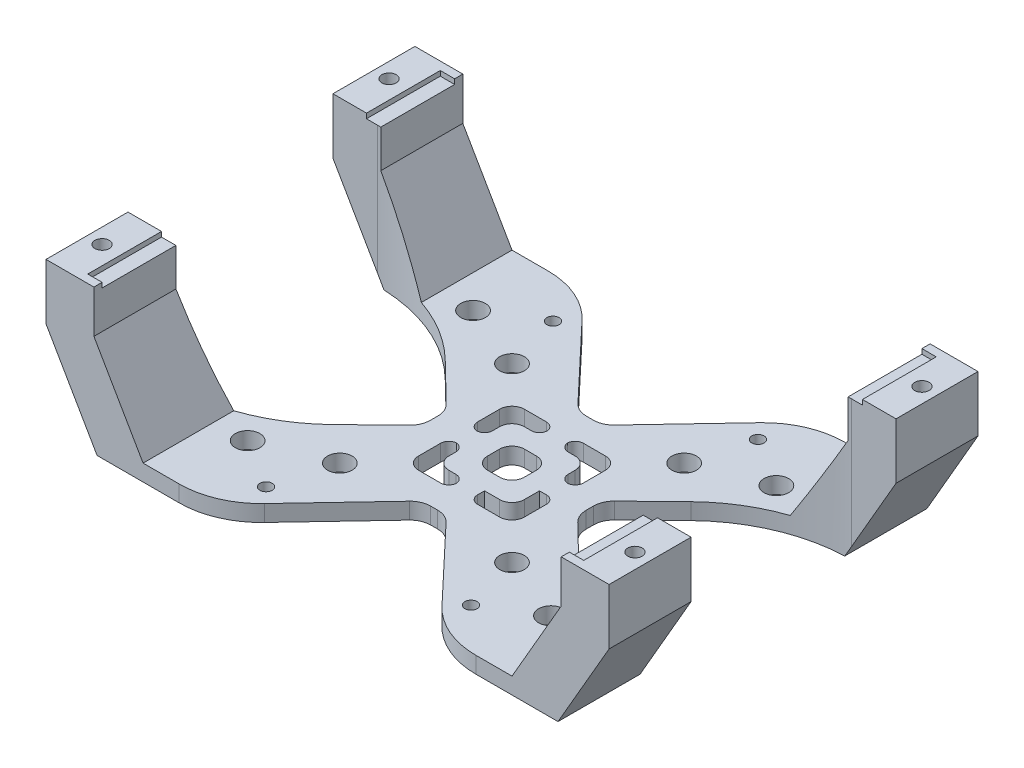
SolidWorks part; units mm, degrees
ref_plane "Спереди" through (0, 0, 0) normal (0, 0, 1) x (1, 0, 0)
ref_plane "Сверху" through (0, 0, 0) normal (0, 1, 0) x (1, 0, 0)
ref_plane "Справа" through (0, 0, 0) normal (1, 0, 0) x (0, 0, -1)
other "Configuration Table"
sketch "Эскиз1" plane through (0, 0, 0) normal (0, 1, 0) x (1, 0, 0)
  line L0 (-1000, 0) -> (49000, 0) construction
  line L1 (0, -1000) -> (0, 49000) construction
  line L2 (19, -0.8894) -> (19, 0.8894)
  line L7 (0, 19) -> (0.8457, 19)
  line L9 (20.5123, 4.4722) -> (40.4877, 23.9172)
  line L10 (4.4797, 20.5658) -> (21.366, 38.4342)
  line L11 (27.65, 39.24) -> (39.65, 31.74)
  line L12 (27.65, -39.24) -> (39.65, -31.74)
  line L13 (4.4797, -20.5658) -> (21.366, -38.4342)
  line L14 (20.5123, -4.4722) -> (40.4877, -23.9172)
  line L15 (0, -19) -> (0.8457, -19)
  line L16 (-20.5123, -4.4722) -> (-40.4877, -23.9172)
  line L17 (-4.4797, -20.5658) -> (-21.366, -38.4342)
  line L18 (-27.65, -39.24) -> (-39.65, -31.74)
  line L19 (-27.65, 39.24) -> (-39.65, 31.74)
  line L20 (-4.4797, 20.5658) -> (-21.366, 38.4342)
  line L21 (-20.5123, 4.4722) -> (-40.4877, 23.9172)
  line L22 (-19, -0.8894) -> (-19, 0.8894)
  line L23 (-0.8457, -19) -> (0, -19)
  line L24 (-0.8457, 19) -> (0, 19)
  line L25 (-21, 21) -> (21, -21) construction
  line L26 (-21, -21) -> (21, 21) construction
  line L27 (-2.5, 9.2035) -> (-2.5, 12.906)
  line L28 (-12.906, -12.906) -> (12.906, -12.906)
  line L29 (-12.906, -12.906) -> (-12.906, 12.906)
  line L30 (-12.906, 12.906) -> (12.906, 12.906)
  line L31 (12.906, -12.906) -> (12.906, 12.906)
  line L32 (-12.906, -12.906) -> (12.906, 12.906) construction
  line L33 (-12.906, 12.906) -> (12.906, -12.906) construction
  line L34 (-9.2035, -9.2035) -> (9.2035, -9.2035)
  line L35 (-9.2035, -9.2035) -> (-9.2035, 9.2035)
  line L36 (-9.2035, 9.2035) -> (9.2035, 9.2035)
  line L37 (9.2035, -9.2035) -> (9.2035, 9.2035)
  line L38 (-9.2035, -9.2035) -> (9.2035, 9.2035) construction
  line L39 (-9.2035, 9.2035) -> (9.2035, -9.2035) construction
  line L40 (-4.4797, -4.4797) -> (4.4797, -4.4797)
  line L41 (-4.4797, -4.4797) -> (-4.4797, 4.4797)
  line L42 (-4.4797, 4.4797) -> (4.4797, 4.4797)
  line L43 (4.4797, -4.4797) -> (4.4797, 4.4797)
  line L44 (-4.4797, -4.4797) -> (4.4797, 4.4797) construction
  line L45 (-4.4797, 4.4797) -> (4.4797, -4.4797) construction
  line L46 (2.5, 9.2035) -> (2.5, 12.906)
  line L47 (2.5, -9.2035) -> (2.5, -12.906)
  line L48 (-2.5, -9.2035) -> (-2.5, -12.906)
  line L49 (-9.2035, -2.5) -> (-12.906, -2.5)
  line L50 (-9.2035, 2.5) -> (-12.906, 2.5)
  line L51 (9.2035, 2.5) -> (12.906, 2.5)
  line L52 (9.2035, -2.5) -> (12.906, -2.5)
  circle A12 centre (25, 35) radius 1.5
  circle A13 centre (21, 21) radius 3
  circle A14 centre (37, 27.5) radius 3
  circle A15 centre (37, 27.5) radius 5
  circle A16 centre (21, 21) radius 5
  circle A17 centre (25, 35) radius 5
  circle A18 centre (25, -35) radius 5
  circle A19 centre (21, -21) radius 5
  circle A20 centre (37, -27.5) radius 5
  circle A21 centre (37, -27.5) radius 3
  circle A22 centre (21, -21) radius 3
  circle A23 centre (25, -35) radius 1.5
  circle A24 centre (-25, -35) radius 1.5
  circle A25 centre (-21, -21) radius 3
  circle A26 centre (-37, -27.5) radius 3
  circle A27 centre (-37, -27.5) radius 5
  circle A28 centre (-21, -21) radius 5
  circle A29 centre (-25, -35) radius 5
  circle A30 centre (-25, 35) radius 5
  circle A31 centre (-21, 21) radius 5
  circle A32 centre (-37, 27.5) radius 5
  circle A33 centre (-37, 27.5) radius 3
  circle A34 centre (-21, 21) radius 3
  circle A35 centre (-25, 35) radius 1.5
  arc A36 (19, 0.8894) -> (20.5123, 4.4722) centre (24, 0.8894) cw
  arc A37 (20.5123, -4.4722) -> (19, -0.8894) centre (24, -0.8894) cw
  arc A38 (4.4797, -20.5658) -> (0.8457, -19) centre (0.8457, -24) ccw
  arc A39 (-4.4797, -20.5658) -> (-0.8457, -19) centre (-0.8457, -24) cw
  arc A40 (-20.5123, -4.4722) -> (-19, -0.8894) centre (-24, -0.8894) ccw
  arc A41 (-20.5123, 4.4722) -> (-19, 0.8894) centre (-24, 0.8894) cw
  arc A42 (0.8457, 19) -> (4.4797, 20.5658) centre (0.8457, 24) ccw
  arc A43 (-4.4797, 20.5658) -> (-0.8457, 19) centre (-0.8457, 24) ccw
  point P41 (19, 0)
  point P71 (-19, 0)
  point P74 (19, 3)
  point P77 (19, -3)
  point P80 (3, -19)
  point P83 (-3, -19)
  point P86 (-19, -3)
  point P89 (-19, 3)
  point P92 (3, 19)
  point P95 (-3, 19)
  point P96 (0, 0)
  point P101 (0, 0)
  point P106 (0, 0)
  dimension "D3" = 6
  dimension "D8" = 37
  dimension "D19" = 5
  dimension "D1" = 3
  dimension "D2" = 6
  dimension "D14" = 10
  dimension "D15" = 10
  dimension "D16" = 10
  dimension "D17" = 5
  dimension "D4" = 35
  dimension "D5" = 25
  dimension "D6" = 21
  dimension "D7" = 21
  dimension "D9" = 27.5
  dimension "D10" = 19
  dimension "D11" = 19
  dimension "D12" = 3
  dimension "D13" = 3
  dimension "D18" = 5
extrude "Бобышка-Вытянуть1" add sketch "Эскиз1" along normal blind 4 contours L19 A32 L21 L22 L16 A27 L18 A29 L17 L23 L15 L13 A18 L12 A20 L14 L2 L9 A15 L11 A17 L10 L7 L24 L20 A30 A31 A28 A16 A19 | A18 A23 | A19 A22 | A20 A21 | A29 A24 | A27 A26 | A28 A25 | A16 A13 | A17 A12 | A15 A14 | A31 A34 | A30 A35 | A32 A33 | L40 L43 L42 L41 | L34 L48 L28 L47 | L35 L50 L29 L49 | L37 L52 L31 L51 | L36 L46 L30 L27 | L35 L34 L37 L36 region at (18.3547, 0, 3.2724) region at (41.4761, 0, 25.6106) region at (32.169, 0, -26.9827) region at (24.3821, 0, 39.8191) region at (29.2495, 0, -37.3553) region at (-24.3821, 0, 39.8191) region at (-20.4854, 0, -36.7957) region at (-41.831, 0, 28.0173) region at (-34.6447, 0, -31.7495) region at (0, 0, -11.0548) region at (-11.0548, 0, 0) region at (11.0548, 0, 0) region at (0, 0, 11.0548) region at (0, 0, 0) region at (16.1414, 0, -21) region at (16.1414, 0, 21) region at (-25.8586, 0, 21) region at (-25.8586, 0, -21)
fillet "Скругление6" radius 3 4 edges at (-4.4797, 2, 4.4797) (4.4797, 2, 4.4797) (4.4797, 2, -4.4797) (-4.4797, 2, -4.4797)
fillet "Скругление7" radius 3 8 edges at (-12.906, 2, 12.906) (12.906, 2, 12.906) (12.906, 2, -12.906) (-12.906, 2, -12.906) (9.2035, 2, 9.2035) (-9.2035, 2, 9.2035) (-9.2035, 2, -9.2035) (9.2035, 2, -9.2035)
fillet "Скругление8" radius 2 14 edges at (-2.5, 2, 12.906) (-2.5, 2, 9.2035) (12.906, 2, 2.5) (12.906, 2, -2.5) (2.5, 2, 12.906) (9.2035, 2, -2.5) (2.5, 2, -9.2035) (2.5, 2, -12.906) (-2.5, 2, -12.906) (-2.5, 2, -9.2035) (-9.2035, 2, -2.5) (-12.906, 2, -2.5) (-9.2035, 2, 2.5) (-12.906, 2, 2.5)
sketch "Эскиз5" plane through (0, 4, 0) normal (0, 1, 0) x (1, 0, 0)
  line L0 (-1000, 0) -> (49000, 0) construction
  line L1 (0, -1000) -> (0, 49000) construction
  line L2 (57.8542, 25) -> (60, 25)
  line L7 (-60, -45) -> (60, -45) construction
  line L8 (-60, -45) -> (-60, 45) construction
  line L9 (-60, 45) -> (60, 45) construction
  line L10 (60, -45) -> (60, 45) construction
  line L11 (-60, -45) -> (60, 45) construction
  line L12 (-60, 45) -> (60, -45) construction
  line L13 (60, 45) -> (65, 45)
  line L14 (60, 45) -> (60, 25)
  line L15 (60, 25) -> (65, 25)
  line L16 (65, 45) -> (65, 25)
  line L17 (20.5123, 4.4722) -> (40.4877, 23.9172) construction
  line L18 (15.9182, 0) -> (29.9529, 13.6622)
  line L19 (0, 15.8255) -> (21.6521, 38.737)
  line L22 (4.4797, 20.5658) -> (21.366, 38.4342) construction
  line L23 (36.1881, 45) -> (65, 45)
  line L24 (36.1881, -45) -> (65, -45)
  line L25 (0, -15.8255) -> (21.6521, -38.737)
  line L26 (15.9182, 0) -> (29.9529, -13.6622)
  line L27 (65, -45) -> (65, -25)
  line L28 (60, -25) -> (65, -25)
  line L29 (60, -45) -> (60, -25)
  line L30 (60, -45) -> (65, -45)
  line L31 (57.8542, -25) -> (60, -25)
  line L32 (60, 45) -> (-60, -45) construction
  line L33 (60, -45) -> (-60, 45) construction
  line L34 (-60, -45) -> (-60, 45) construction
  line L35 (-57.8542, -25) -> (-60, -25)
  line L36 (-60, -45) -> (-65, -45)
  line L37 (-60, -45) -> (-60, -25)
  line L38 (-60, -25) -> (-65, -25)
  line L39 (-65, -45) -> (-65, -25)
  line L40 (-15.9182, 0) -> (-29.9529, -13.6622)
  line L41 (0, -15.8255) -> (-21.6521, -38.737)
  line L42 (-36.1881, -45) -> (-65, -45)
  line L43 (-36.1881, 45) -> (-65, 45)
  line L44 (0, 15.8255) -> (-21.6521, 38.737)
  line L45 (-15.9182, 0) -> (-29.9529, 13.6622)
  line L46 (-65, 45) -> (-65, 25)
  line L47 (-60, 25) -> (-65, 25)
  line L48 (-60, 45) -> (-60, 25)
  line L49 (-60, 45) -> (-65, 45)
  line L50 (-57.8542, 25) -> (-60, 25)
  line L67 (-4.4797, 20.5658) -> (-21.366, 38.4342)
  line L68 (-27.65, 39.24) -> (-39.65, 31.74)
  line L69 (-40.4877, 23.9172) -> (-20.5123, 4.4722)
  line L70 (-19, 0.8894) -> (-19, -0.8894)
  line L71 (-20.5123, -4.4722) -> (-40.4877, -23.9172)
  line L72 (-39.65, -31.74) -> (-27.65, -39.24)
  line L73 (-21.366, -38.4342) -> (-4.4797, -20.5658)
  line L74 (-0.8457, -19) -> (0.8457, -19)
  line L75 (4.4797, -20.5658) -> (21.366, -38.4342)
  line L76 (27.65, -39.24) -> (39.65, -31.74)
  line L77 (40.4877, -23.9172) -> (20.5123, -4.4722)
  line L78 (19, -0.8894) -> (19, 0.8894)
  line L79 (20.5123, 4.4722) -> (40.4877, 23.9172)
  line L80 (39.65, 31.74) -> (27.65, 39.24)
  line L81 (21.366, 38.4342) -> (4.4797, 20.5658)
  line L82 (0.8457, 19) -> (-0.8457, 19)
  line L83 (-4.4797, 20.5658) -> (-21.366, 38.4342)
  line L84 (-27.65, 39.24) -> (-39.65, 31.74)
  line L85 (-40.4877, 23.9172) -> (-20.5123, 4.4722)
  line L86 (-19, 0.8894) -> (-19, -0.8894)
  line L87 (-20.5123, -4.4722) -> (-40.4877, -23.9172)
  line L88 (-39.65, -31.74) -> (-27.65, -39.24)
  line L89 (-21.366, -38.4342) -> (-4.4797, -20.5658)
  line L90 (-0.8457, -19) -> (0.8457, -19)
  line L91 (4.4797, -20.5658) -> (21.366, -38.4342)
  line L92 (27.65, -39.24) -> (39.65, -31.74)
  line L93 (40.4877, -23.9172) -> (20.5123, -4.4722)
  line L94 (19, -0.8894) -> (19, 0.8894)
  line L95 (20.5123, 4.4722) -> (40.4877, 23.9172)
  line L96 (39.65, 31.74) -> (27.65, 39.24)
  line L97 (21.366, 38.4342) -> (4.4797, 20.5658)
  line L98 (0.8457, 19) -> (-0.8457, 19)
  arc A0 (57.8542, 25) -> (29.9529, 13.6622) centre (57.8542, -15) ccw
  arc A1 (36.1881, 45) -> (21.6521, 38.737) centre (36.1881, 25) ccw
  arc A2 (36.1881, -45) -> (21.6521, -38.737) centre (36.1881, -25) cw
  arc A3 (57.8542, -25) -> (29.9529, -13.6622) centre (57.8542, 15) cw
  arc A4 (-57.8542, -25) -> (-29.9529, -13.6622) centre (-57.8542, 15) ccw
  arc A5 (-36.1881, -45) -> (-21.6521, -38.737) centre (-36.1881, -25) ccw
  arc A6 (-36.1881, 45) -> (-21.6521, 38.737) centre (-36.1881, 25) cw
  arc A7 (-57.8542, 25) -> (-29.9529, 13.6622) centre (-57.8542, -15) cw
  circle A8 centre (-37, 27.5) radius 3 construction
  circle A9 centre (-25, 35) radius 1.5 construction
  circle A10 centre (-21, 21) radius 3 construction
  circle A11 centre (-37, 27.5) radius 3
  circle A12 centre (-25, 35) radius 1.5
  circle A13 centre (-21, 21) radius 3
  arc A24 (-4.4797, 20.5658) -> (-0.8457, 19) centre (-0.8457, 24) ccw
  arc A25 (-21.366, 38.4342) -> (-27.65, 39.24) centre (-25, 35) ccw
  arc A26 (-39.65, 31.74) -> (-40.4877, 23.9172) centre (-37, 27.5) ccw
  arc A27 (-19, 0.8894) -> (-20.5123, 4.4722) centre (-24, 0.8894) ccw
  arc A28 (-20.5123, -4.4722) -> (-19, -0.8894) centre (-24, -0.8894) ccw
  arc A29 (-40.4877, -23.9172) -> (-39.65, -31.74) centre (-37, -27.5) ccw
  arc A30 (-27.65, -39.24) -> (-21.366, -38.4342) centre (-25, -35) ccw
  arc A31 (-0.8457, -19) -> (-4.4797, -20.5658) centre (-0.8457, -24) ccw
  arc A32 (4.4797, -20.5658) -> (0.8457, -19) centre (0.8457, -24) ccw
  arc A33 (21.366, -38.4342) -> (27.65, -39.24) centre (25, -35) ccw
  arc A34 (39.65, -31.74) -> (40.4877, -23.9172) centre (37, -27.5) ccw
  arc A35 (19, -0.8894) -> (20.5123, -4.4722) centre (24, -0.8894) ccw
  arc A36 (20.5123, 4.4722) -> (19, 0.8894) centre (24, 0.8894) ccw
  arc A37 (40.4877, 23.9172) -> (39.65, 31.74) centre (37, 27.5) ccw
  arc A38 (27.65, 39.24) -> (21.366, 38.4342) centre (25, 35) ccw
  arc A39 (0.8457, 19) -> (4.4797, 20.5658) centre (0.8457, 24) ccw
  arc A40 (-4.4797, 20.5658) -> (-0.8457, 19) centre (-0.8457, 24) ccw
  arc A41 (-21.366, 38.4342) -> (-27.65, 39.24) centre (-25, 35) ccw
  arc A42 (-39.65, 31.74) -> (-40.4877, 23.9172) centre (-37, 27.5) ccw
  arc A43 (-19, 0.8894) -> (-20.5123, 4.4722) centre (-24, 0.8894) ccw
  arc A44 (-20.5123, -4.4722) -> (-19, -0.8894) centre (-24, -0.8894) ccw
  arc A45 (-40.4877, -23.9172) -> (-39.65, -31.74) centre (-37, -27.5) ccw
  arc A46 (-27.65, -39.24) -> (-21.366, -38.4342) centre (-25, -35) ccw
  arc A47 (-0.8457, -19) -> (-4.4797, -20.5658) centre (-0.8457, -24) ccw
  arc A48 (4.4797, -20.5658) -> (0.8457, -19) centre (0.8457, -24) ccw
  arc A49 (21.366, -38.4342) -> (27.65, -39.24) centre (25, -35) ccw
  arc A50 (39.65, -31.74) -> (40.4877, -23.9172) centre (37, -27.5) ccw
  arc A51 (19, -0.8894) -> (20.5123, -4.4722) centre (24, -0.8894) ccw
  arc A52 (20.5123, 4.4722) -> (19, 0.8894) centre (24, 0.8894) ccw
  arc A53 (40.4877, 23.9172) -> (39.65, 31.74) centre (37, 27.5) ccw
  arc A54 (27.65, 39.24) -> (21.366, 38.4342) centre (25, 35) ccw
  arc A55 (0.8457, 19) -> (4.4797, 20.5658) centre (0.8457, 24) ccw
  point P4 (0, 0)
  point P6 (0, 0)
  point P24 (41.6, 25)
  point P30 (13.3997, 30.0046)
  point P35 (27.5709, 45)
  point P46 (27.5709, -45)
  point P47 (13.3997, -30.0046)
  point P48 (41.6, -25)
  point P68 (-41.6, -25)
  point P69 (-13.3997, -30.0046)
  point P70 (-27.5709, -45)
  point P71 (-27.5709, 45)
  point P72 (-13.3997, 30.0046)
  point P73 (-41.6, 25)
  dimension "D3" = 40
  dimension "D4" = 20
  dimension "D1" = 120
  dimension "D2" = 90
  dimension "D5" = 5
  dimension "D6" = 20
  dimension "D7" = 0
extrude "Бобышка-Вытянуть3" add sketch "Эскиз5" against normal up to surface (4 mm away) contours A42 L84 A41 L44 A6 L43 L48 L50 A7 L85 | L48 L43 L46 L47 | A46 L88 A45 L87 A4 L35 L37 L42 A5 L41 | L39 L36 L37 L38 | A50 L92 A49 L25 A2 L24 L29 L31 A3 L93 | L29 L24 L27 L28 | A54 L96 A53 L95 A0 L2 L14 L23 A1 L19 | L16 L13 L14 L15 region at (46.1694, 4, -35.4744) region at (62.5, 4, -35) region at (46.1694, 4, 35.4744) region at (62.5, 4, 35) region at (-46.1694, 4, -35.4744) region at (-62.5, 4, -35) region at (-46.1694, 4, 35.4744) region at (-62.5, 4, 35) up to face at (8.1977, 0, 8.1977)
sketch "Эскиз6" plane through (0, 4, 0) normal (0, 1, 0) x (1, 0, 0)
  line L0 (-1000, 0) -> (49000, 0) construction
  line L1 (65, 45) -> (60, 45)
  line L2 (65, 45) -> (65, 25)
  line L3 (65, 25) -> (60, 25)
  line L4 (-9.2035, -6.2035) -> (-9.2035, -4.5)
  line L5 (-4.5, -9.2035) -> (-6.2035, -9.2035)
  line L6 (-9.906, -12.906) -> (-4.5, -12.906)
  line L7 (-12.906, -4.5) -> (-12.906, -9.906)
  line L8 (-9.2035, -6.2035) -> (-9.2035, -4.5)
  line L9 (-4.5, -9.2035) -> (-6.2035, -9.2035)
  line L10 (-9.906, -12.906) -> (-4.5, -12.906)
  line L11 (-12.906, -4.5) -> (-12.906, -9.906)
  line L12 (4.4797, -1.4797) -> (4.4797, 1.4797)
  line L13 (-1.4797, -4.4797) -> (1.4797, -4.4797)
  line L14 (-4.4797, 1.4797) -> (-4.4797, -1.4797)
  line L15 (1.4797, 4.4797) -> (-1.4797, 4.4797)
  line L16 (4.4797, -1.4797) -> (4.4797, 1.4797)
  line L17 (-1.4797, -4.4797) -> (1.4797, -4.4797)
  line L18 (-4.4797, 1.4797) -> (-4.4797, -1.4797)
  line L19 (1.4797, 4.4797) -> (-1.4797, 4.4797)
  line L20 (9.2035, 6.2035) -> (9.2035, 4.5)
  line L21 (4.5, 9.2035) -> (6.2035, 9.2035)
  line L22 (9.906, 12.906) -> (4.5, 12.906)
  line L23 (12.906, 4.5) -> (12.906, 9.906)
  line L24 (9.2035, 6.2035) -> (9.2035, 4.5)
  line L25 (4.5, 9.2035) -> (6.2035, 9.2035)
  line L26 (9.906, 12.906) -> (4.5, 12.906)
  line L27 (12.906, 4.5) -> (12.906, 9.906)
  line L28 (-6.2035, 9.2035) -> (-4.5, 9.2035)
  line L29 (-9.2035, 4.5) -> (-9.2035, 6.2035)
  line L30 (-12.906, 9.906) -> (-12.906, 4.5)
  line L31 (-4.5, 12.906) -> (-9.906, 12.906)
  line L32 (-6.2035, 9.2035) -> (-4.5, 9.2035)
  line L33 (-9.2035, 4.5) -> (-9.2035, 6.2035)
  line L34 (-12.906, 9.906) -> (-12.906, 4.5)
  line L35 (-4.5, 12.906) -> (-9.906, 12.906)
  line L36 (60, 45) -> (60, 25)
  line L37 (0, -1000) -> (0, 49000) construction
  line L38 (6.2035, -9.2035) -> (2.5, -9.2035)
  line L39 (9.2035, -2.5) -> (9.2035, -6.2035)
  line L40 (10.906, -2.5) -> (9.2035, -2.5)
  line L41 (12.906, -9.906) -> (12.906, -4.5)
  line L42 (4.5, -12.906) -> (9.906, -12.906)
  line L43 (2.5, -9.2035) -> (2.5, -10.906)
  line L44 (6.2035, -9.2035) -> (2.5, -9.2035)
  line L45 (9.2035, -2.5) -> (9.2035, -6.2035)
  line L46 (10.906, -2.5) -> (9.2035, -2.5)
  line L47 (12.906, -9.906) -> (12.906, -4.5)
  line L48 (4.5, -12.906) -> (9.906, -12.906)
  line L49 (2.5, -9.2035) -> (2.5, -10.906)
  line L50 (57, 45) -> (57, 24.9909)
  line L51 (57, -45) -> (57, -24.9909)
  line L52 (-57, -45) -> (-57, -24.9909)
  line L53 (-57, 45) -> (-57, 24.9909)
  line L68 (4.4797, -20.5658) -> (21.6521, -38.737)
  line L69 (36.1881, -45) -> (65, -45)
  line L70 (65, -45) -> (65, -25)
  line L71 (65, -25) -> (57.8542, -25)
  line L72 (29.9529, -13.6622) -> (20.5123, -4.4722)
  line L73 (19, -0.8894) -> (19, 0.8894)
  line L74 (20.5123, 4.4722) -> (29.9529, 13.6622)
  line L75 (57.8542, 25) -> (65, 25)
  line L76 (65, 25) -> (65, 45)
  line L77 (65, 45) -> (36.1881, 45)
  line L78 (21.6521, 38.737) -> (4.4797, 20.5658)
  line L79 (0.8457, 19) -> (-0.8457, 19)
  line L80 (-4.4797, 20.5658) -> (-21.6521, 38.737)
  line L81 (-36.1881, 45) -> (-65, 45)
  line L82 (-65, 45) -> (-65, 25)
  line L83 (-65, 25) -> (-57.8542, 25)
  line L84 (-29.9529, 13.6622) -> (-20.5123, 4.4722)
  line L85 (-19, 0.8894) -> (-19, -0.8894)
  line L86 (-20.5123, -4.4722) -> (-29.9529, -13.6622)
  line L87 (-57.8542, -25) -> (-65, -25)
  line L88 (-65, -25) -> (-65, -45)
  line L89 (-65, -45) -> (-36.1881, -45)
  line L90 (-21.6521, -38.737) -> (-4.4797, -20.5658)
  line L91 (-0.8457, -19) -> (0.8457, -19)
  line L92 (4.4797, -20.5658) -> (21.6521, -38.737)
  line L93 (36.1881, -45) -> (65, -45)
  line L94 (65, -45) -> (65, -25)
  line L95 (65, -25) -> (57.8542, -25)
  line L96 (29.9529, -13.6622) -> (20.5123, -4.4722)
  line L97 (19, -0.8894) -> (19, 0.8894)
  line L98 (20.5123, 4.4722) -> (29.9529, 13.6622)
  line L99 (57.8542, 25) -> (65, 25)
  line L100 (65, 25) -> (65, 45)
  line L101 (65, 45) -> (36.1881, 45)
  line L102 (21.6521, 38.737) -> (4.4797, 20.5658)
  line L103 (0.8457, 19) -> (-0.8457, 19)
  line L104 (-4.4797, 20.5658) -> (-21.6521, 38.737)
  line L105 (-36.1881, 45) -> (-65, 45)
  line L106 (-65, 45) -> (-65, 25)
  line L107 (-65, 25) -> (-57.8542, 25)
  line L108 (-29.9529, 13.6622) -> (-20.5123, 4.4722)
  line L109 (-19, 0.8894) -> (-19, -0.8894)
  line L110 (-20.5123, -4.4722) -> (-29.9529, -13.6622)
  line L111 (-57.8542, -25) -> (-65, -25)
  line L112 (-65, -25) -> (-65, -45)
  line L113 (-65, -45) -> (-36.1881, -45)
  line L114 (-21.6521, -38.737) -> (-4.4797, -20.5658)
  line L115 (-0.8457, -19) -> (0.8457, -19)
  circle A1 centre (-21, 21) radius 3
  circle A2 centre (-21, 21) radius 3
  circle A3 centre (-21, -21) radius 3
  circle A4 centre (-21, -21) radius 3
  circle A5 centre (21, 21) radius 3
  arc A6 (-9.2035, -6.2035) -> (-6.2035, -9.2035) centre (-6.2035, -6.2035) ccw
  arc A7 (-2.5055, -11.0548) -> (-4.5, -9.2035) centre (-4.5, -11.2035) ccw
  arc A8 (-4.5, -12.906) -> (-2.5055, -11.0548) centre (-4.5, -10.906) ccw
  arc A9 (-12.906, -9.906) -> (-9.906, -12.906) centre (-9.906, -9.906) ccw
  arc A10 (-11.0548, -2.5055) -> (-12.906, -4.5) centre (-10.906, -4.5) ccw
  arc A11 (-9.2035, -4.5) -> (-11.0548, -2.5055) centre (-11.2035, -4.5) ccw
  arc A12 (-9.2035, -6.2035) -> (-6.2035, -9.2035) centre (-6.2035, -6.2035) ccw
  arc A13 (-2.5055, -11.0548) -> (-4.5, -9.2035) centre (-4.5, -11.2035) ccw
  arc A14 (-4.5, -12.906) -> (-2.5055, -11.0548) centre (-4.5, -10.906) ccw
  arc A15 (-12.906, -9.906) -> (-9.906, -12.906) centre (-9.906, -9.906) ccw
  arc A16 (-11.0548, -2.5055) -> (-12.906, -4.5) centre (-10.906, -4.5) ccw
  arc A17 (-9.2035, -4.5) -> (-11.0548, -2.5055) centre (-11.2035, -4.5) ccw
  circle A18 centre (21, 21) radius 3
  circle A19 centre (21, -21) radius 3
  circle A20 centre (21, -21) radius 3
  circle A21 centre (25, 35) radius 1.5
  circle A22 centre (25, 35) radius 1.5
  circle A23 centre (37, 27.5) radius 3
  circle A24 centre (37, 27.5) radius 3
  circle A25 centre (37, -27.5) radius 3
  circle A26 centre (37, -27.5) radius 3
  circle A27 centre (25, -35) radius 1.5
  circle A28 centre (25, -35) radius 1.5
  circle A29 centre (-25, -35) radius 1.5
  circle A30 centre (-25, -35) radius 1.5
  circle A31 centre (-37, -27.5) radius 3
  circle A32 centre (-37, -27.5) radius 3
  circle A33 centre (-37, 27.5) radius 3
  circle A34 centre (-37, 27.5) radius 3
  circle A35 centre (-25, 35) radius 1.5
  circle A36 centre (-25, 35) radius 1.5
  arc A40 (1.4797, -4.4797) -> (4.4797, -1.4797) centre (1.4797, -1.4797) ccw
  arc A41 (-4.4797, -1.4797) -> (-1.4797, -4.4797) centre (-1.4797, -1.4797) ccw
  arc A42 (-1.4797, 4.4797) -> (-4.4797, 1.4797) centre (-1.4797, 1.4797) ccw
  arc A43 (4.4797, 1.4797) -> (1.4797, 4.4797) centre (1.4797, 1.4797) ccw
  arc A44 (1.4797, -4.4797) -> (4.4797, -1.4797) centre (1.4797, -1.4797) ccw
  arc A45 (-4.4797, -1.4797) -> (-1.4797, -4.4797) centre (-1.4797, -1.4797) ccw
  arc A46 (-1.4797, 4.4797) -> (-4.4797, 1.4797) centre (-1.4797, 1.4797) ccw
  arc A47 (4.4797, 1.4797) -> (1.4797, 4.4797) centre (1.4797, 1.4797) ccw
  arc A48 (6.2035, -9.2035) -> (9.2035, -6.2035) centre (6.2035, -6.2035) ccw
  arc A49 (12.906, -4.5) -> (10.906, -2.5) centre (10.906, -4.5) ccw
  arc A50 (11.0548, 2.5055) -> (12.906, 4.5) centre (10.906, 4.5) ccw
  arc A51 (9.2035, 4.5) -> (11.0548, 2.5055) centre (11.2035, 4.5) ccw
  arc A52 (9.2035, 6.2035) -> (6.2035, 9.2035) centre (6.2035, 6.2035) ccw
  arc A53 (2.5055, 11.0548) -> (4.5, 9.2035) centre (4.5, 11.2035) ccw
  arc A54 (4.5, 12.906) -> (2.5055, 11.0548) centre (4.5, 10.906) ccw
  arc A55 (12.906, 9.906) -> (9.906, 12.906) centre (9.906, 9.906) ccw
  arc A56 (11.0548, 2.5055) -> (12.906, 4.5) centre (10.906, 4.5) ccw
  arc A57 (9.2035, 4.5) -> (11.0548, 2.5055) centre (11.2035, 4.5) ccw
  arc A58 (9.2035, 6.2035) -> (6.2035, 9.2035) centre (6.2035, 6.2035) ccw
  arc A59 (2.5055, 11.0548) -> (4.5, 9.2035) centre (4.5, 11.2035) ccw
  arc A60 (4.5, 12.906) -> (2.5055, 11.0548) centre (4.5, 10.906) ccw
  arc A61 (12.906, 9.906) -> (9.906, 12.906) centre (9.906, 9.906) ccw
  arc A62 (-6.2035, 9.2035) -> (-9.2035, 6.2035) centre (-6.2035, 6.2035) ccw
  arc A63 (-11.0548, 2.5055) -> (-9.2035, 4.5) centre (-11.2035, 4.5) ccw
  arc A64 (-12.906, 4.5) -> (-11.0548, 2.5055) centre (-10.906, 4.5) ccw
  arc A65 (-9.906, 12.906) -> (-12.906, 9.906) centre (-9.906, 9.906) ccw
  arc A66 (-2.5055, 11.0548) -> (-4.5, 12.906) centre (-4.5, 10.906) ccw
  arc A67 (-4.5, 9.2035) -> (-2.5055, 11.0548) centre (-4.5, 11.2035) ccw
  arc A68 (-6.2035, 9.2035) -> (-9.2035, 6.2035) centre (-6.2035, 6.2035) ccw
  arc A69 (-11.0548, 2.5055) -> (-9.2035, 4.5) centre (-11.2035, 4.5) ccw
  arc A70 (-12.906, 4.5) -> (-11.0548, 2.5055) centre (-10.906, 4.5) ccw
  arc A71 (-9.906, 12.906) -> (-12.906, 9.906) centre (-9.906, 9.906) ccw
  arc A72 (-2.5055, 11.0548) -> (-4.5, 12.906) centre (-4.5, 10.906) ccw
  arc A73 (-4.5, 9.2035) -> (-2.5055, 11.0548) centre (-4.5, 11.2035) ccw
  arc A74 (9.906, -12.906) -> (12.906, -9.906) centre (9.906, -9.906) ccw
  arc A75 (2.5, -10.906) -> (4.5, -12.906) centre (4.5, -10.906) ccw
  arc A76 (6.2035, -9.2035) -> (9.2035, -6.2035) centre (6.2035, -6.2035) ccw
  arc A77 (12.906, -4.5) -> (10.906, -2.5) centre (10.906, -4.5) ccw
  arc A78 (9.906, -12.906) -> (12.906, -9.906) centre (9.906, -9.906) ccw
  arc A79 (2.5, -10.906) -> (4.5, -12.906) centre (4.5, -10.906) ccw
  arc A92 (21.6521, -38.737) -> (36.1881, -45) centre (36.1881, -25) ccw
  arc A93 (29.9529, -13.6622) -> (57.8542, -25) centre (57.8542, 15) ccw
  arc A94 (19, -0.8894) -> (20.5123, -4.4722) centre (24, -0.8894) ccw
  arc A95 (20.5123, 4.4722) -> (19, 0.8894) centre (24, 0.8894) ccw
  arc A96 (57.8542, 25) -> (29.9529, 13.6622) centre (57.8542, -15) ccw
  arc A97 (36.1881, 45) -> (21.6521, 38.737) centre (36.1881, 25) ccw
  arc A98 (0.8457, 19) -> (4.4797, 20.5658) centre (0.8457, 24) ccw
  arc A99 (-4.4797, 20.5658) -> (-0.8457, 19) centre (-0.8457, 24) ccw
  arc A100 (-21.6521, 38.737) -> (-36.1881, 45) centre (-36.1881, 25) ccw
  arc A101 (-29.9529, 13.6622) -> (-57.8542, 25) centre (-57.8542, -15) ccw
  arc A102 (-19, 0.8894) -> (-20.5123, 4.4722) centre (-24, 0.8894) ccw
  arc A103 (-20.5123, -4.4722) -> (-19, -0.8894) centre (-24, -0.8894) ccw
  arc A104 (-57.8542, -25) -> (-29.9529, -13.6622) centre (-57.8542, 15) ccw
  arc A105 (-36.1881, -45) -> (-21.6521, -38.737) centre (-36.1881, -25) ccw
  arc A106 (-0.8457, -19) -> (-4.4797, -20.5658) centre (-0.8457, -24) ccw
  arc A107 (4.4797, -20.5658) -> (0.8457, -19) centre (0.8457, -24) ccw
  arc A108 (21.6521, -38.737) -> (36.1881, -45) centre (36.1881, -25) ccw
  arc A109 (29.9529, -13.6622) -> (57.8542, -25) centre (57.8542, 15) ccw
  arc A110 (19, -0.8894) -> (20.5123, -4.4722) centre (24, -0.8894) ccw
  arc A111 (20.5123, 4.4722) -> (19, 0.8894) centre (24, 0.8894) ccw
  arc A112 (57.8542, 25) -> (29.9529, 13.6622) centre (57.8542, -15) ccw
  arc A113 (36.1881, 45) -> (21.6521, 38.737) centre (36.1881, 25) ccw
  arc A114 (0.8457, 19) -> (4.4797, 20.5658) centre (0.8457, 24) ccw
  arc A115 (-4.4797, 20.5658) -> (-0.8457, 19) centre (-0.8457, 24) ccw
  arc A116 (-21.6521, 38.737) -> (-36.1881, 45) centre (-36.1881, 25) ccw
  arc A117 (-29.9529, 13.6622) -> (-57.8542, 25) centre (-57.8542, -15) ccw
  arc A118 (-19, 0.8894) -> (-20.5123, 4.4722) centre (-24, 0.8894) ccw
  arc A119 (-20.5123, -4.4722) -> (-19, -0.8894) centre (-24, -0.8894) ccw
  arc A120 (-57.8542, -25) -> (-29.9529, -13.6622) centre (-57.8542, 15) ccw
  arc A121 (-36.1881, -45) -> (-21.6521, -38.737) centre (-36.1881, -25) ccw
  arc A122 (-0.8457, -19) -> (-4.4797, -20.5658) centre (-0.8457, -24) ccw
  arc A123 (4.4797, -20.5658) -> (0.8457, -19) centre (0.8457, -24) ccw
  dimension "D19" = 5
  dimension "D20" = 3
  dimension "D1" = 0
  dimension "D2" = 0
  dimension "D3" = 0
  dimension "D4" = 0
  dimension "D5" = 0
  dimension "D6" = 0
  dimension "D7" = 0
  dimension "D8" = 0
  dimension "D9" = 0
  dimension "D10" = 0
  dimension "D11" = 0
  dimension "D12" = 0
  dimension "D13" = 0
  dimension "D14" = 0
  dimension "D15" = 0
  dimension "D16" = 0
  dimension "D17" = 0
  dimension "D18" = 0
extrude "Бобышка-Вытянуть4" add sketch "Эскиз6" along normal blind 30 contours A120 L111 L112 L113 L52 | A117 L53 L105 L106 L107 | L1 L36 L3 L2 | A112 L99 L36 L101 L50 | A109 L51 L93 L94 L95 region at (62.5, 4, -35) region at (58.4999, 4, -34.9996) region at (60.9999, 4, 34.9998) region at (-60.9999, 4, -34.9998) region at (-60.9999, 4, 34.9998)
sketch "Эскиз7" plane through (0, 34, 0) normal (0, 1, 0) x (1, 0, 0)
  line L0 (-57.8542, -25) -> (-65, -25) construction
  line L1 (-60.5, -43) -> (60.5, -43)
  line L2 (-60.5, -43) -> (-60.5, 43)
  line L3 (-60.5, 43) -> (60.5, 43)
  line L4 (60.5, -43) -> (60.5, 43)
  line L5 (-60.5, -43) -> (60.5, 43) construction
  line L6 (-60.5, 43) -> (60.5, -43) construction
  line L7 (-65, -25) -> (-65, -45) construction
  line L8 (-65, -45) -> (-57, -45) construction
  line L9 (-57, -45) -> (-57, -24.9909) construction
  line L10 (57, -24.9909) -> (57, -45) construction
  line L11 (57, -45) -> (65, -45) construction
  line L12 (65, -45) -> (65, -25) construction
  line L13 (65, -25) -> (57.8542, -25) construction
  line L14 (65, 45) -> (57, 45) construction
  line L15 (57, 45) -> (57, 24.9909) construction
  line L16 (57.8542, 25) -> (65, 25) construction
  line L17 (65, 25) -> (65, 45) construction
  line L18 (-57, 24.9909) -> (-57, 45) construction
  line L19 (-57, 45) -> (-65, 45) construction
  line L20 (-65, 45) -> (-65, 25) construction
  line L21 (-65, 25) -> (-57.8542, 25) construction
  line L22 (-57.8542, -25) -> (-65, -25)
  line L23 (-65, -25) -> (-65, -45)
  line L24 (-65, -45) -> (-57, -45)
  line L25 (-57, -45) -> (-57, -24.9909)
  line L26 (57, -24.9909) -> (57, -45)
  line L27 (57, -45) -> (65, -45)
  line L28 (65, -45) -> (65, -25)
  line L29 (65, -25) -> (57.8542, -25)
  line L30 (65, 45) -> (57, 45)
  line L31 (57, 45) -> (57, 24.9909)
  line L32 (57.8542, 25) -> (65, 25)
  line L33 (65, 25) -> (65, 45)
  line L34 (-57, 24.9909) -> (-57, 45)
  line L35 (-57, 45) -> (-65, 45)
  line L36 (-65, 45) -> (-65, 25)
  line L37 (-65, 25) -> (-57.8542, 25)
  arc A0 (-57.8542, -25) -> (-57, -24.9909) centre (-57.8542, 15) ccw construction
  arc A1 (57, -24.9909) -> (57.8542, -25) centre (57.8542, 15) ccw construction
  arc A2 (57.8542, 25) -> (57, 24.9909) centre (57.8542, -15) ccw construction
  arc A3 (-57, 24.9909) -> (-57.8542, 25) centre (-57.8542, -15) ccw construction
  arc A4 (-57.8542, -25) -> (-57, -24.9909) centre (-57.8542, 15) ccw
  arc A5 (57, -24.9909) -> (57.8542, -25) centre (57.8542, 15) ccw
  arc A6 (57.8542, 25) -> (57, 24.9909) centre (57.8542, -15) ccw
  arc A7 (-57, 24.9909) -> (-57.8542, 25) centre (-57.8542, -15) ccw
  point P0 (0, 0)
  line M6 (57, -24.9909) -> (57, -45)
  line M7 (57, -45) -> (65, -45)
  line M8 (65, -45) -> (65, -25)
  line M9 (65, -25) -> (57.8542, -25)
  dimension "D1" = 121
  dimension "D2" = 86
extrude "Бобышка-Вытянуть5" add sketch "Эскиз7" along normal blind 1.2 contours L36 L37 L2 L3 L34 L35 | L24 L25 L1 L2 L22 L23 | L4 L1 M6 M7 M8 M9 | L32 L33 L30 L31 L3 L4 region at (-62.4613, 34, 35.6495) region at (62.4613, 34, 35.6495) region at (-62.4613, 34, -35.6495) region at (62.4613, 34, -35.6495)
sketch "Эскиз8" plane through (0, 0, 25) normal (0, 0, -1) x (-1, 0, 0)
  line L0 (65, 15.2) -> (68.6859, 21.5841)
  line L1 (65, 0) -> (65, 35.2) construction
  line L2 (68.6859, 21.5841) -> (68.6859, 35.2)
  line L3 (68.6859, 35.2) -> (65, 35.2)
  line L4 (68.6859, 35.2) -> (65, 35.2)
  line L8 (57.8542, 0) -> (65, 0)
  line L9 (65, 0) -> (65, 35.2)
  line L10 (65, 35.2) -> (60.5, 35.2)
  line L11 (60.5, 35.2) -> (60.5, 34)
  line L12 (60.5, 34) -> (57.8542, 34)
  line L13 (57.8542, 34) -> (57.8542, 0)
  line L14 (57.8542, 0) -> (65, 0)
  line L15 (65, 0) -> (65, 35.2)
  line L16 (65, 35.2) -> (60.5, 35.2)
  line L17 (60.5, 35.2) -> (60.5, 34)
  line L18 (60.5, 34) -> (57.8542, 34)
  line L19 (57.8542, 34) -> (57.8542, 0)
  line M11 (65, 0) -> (65, 35.2)
  dimension "D2" = 30
  dimension "D3" = 20
  dimension "D1" = 0
extrude "Бобышка-Вытянуть6" add sketch "Эскиз8" against normal up to surface (20 mm away) contours L2 L3 L0 M11 region at (-66.7263, 26.695, 25) up to face at (-52.7294, 13.0667, 45)
mirror "Зеркальное отражение1" about plane through (0, 0, 0) normal (1, 0, 0) of "Бобышка-Вытянуть6"
sketch "Эскиз10" plane through (0, 0, -45) normal (0, 0, -1) x (-1, 0, 0)
  line L0 (57.8542, 0) -> (65, 0) construction
  line L1 (65, 0) -> (65, 15.2) construction
  line L2 (65, 15.2) -> (68.6859, 21.5841) construction
  line L3 (68.6859, 21.5841) -> (68.6859, 35.2) construction
  line L4 (68.6859, 35.2) -> (60.5, 35.2) construction
  line L5 (60.5, 35.2) -> (60.5, 34) construction
  line L6 (60.5, 34) -> (57.8542, 34) construction
  line L7 (57.8542, 34) -> (57.8542, 0) construction
  line L8 (36.1881, 0) -> (65, 0) construction
  line L9 (65, 0) -> (65, 35.2) construction
  line L10 (65, 35.2) -> (57, 35.2) construction
  line L11 (57, 35.2) -> (57, 4) construction
  line L12 (57, 4) -> (36.1881, 4) construction
  line L13 (36.1881, 4) -> (36.1881, 0) construction
  line L14 (57.8542, 0) -> (65, 0)
  line L15 (65, 0) -> (65, 15.2)
  line L16 (65, 15.2) -> (68.6859, 21.5841)
  line L17 (68.6859, 21.5841) -> (68.6859, 35.2)
  line L18 (68.6859, 35.2) -> (60.5, 35.2)
  line L19 (60.5, 35.2) -> (60.5, 34)
  line L20 (60.5, 34) -> (57.8542, 34)
  line L21 (57.8542, 34) -> (57.8542, 0)
  line L22 (36.1881, 0) -> (65, 0)
  line L23 (65, 0) -> (65, 35.2)
  line L24 (65, 35.2) -> (57, 35.2)
  line L25 (57, 35.2) -> (57, 4)
  line L26 (57, 4) -> (36.1881, 4)
  line L27 (36.1881, 4) -> (36.1881, 0)
  line M10 (65, 0) -> (65, 35.2)
extrude "Бобышка-Вытянуть7" add sketch "Эскиз10" against normal up to surface (20 mm away) contours L17 L18 L16 M10 region at (-66.7263, 26.695, -45) up to face at (-61.1181, 23.0667, -25)
mirror "Зеркальное отражение12" about plane through (0, 0, 0) normal (1, 0, 0) of "Бобышка-Вытянуть7"
sketch "Эскиз11" plane through (0, 35.2, 0) normal (0, 1, 0) x (1, 0, 0)
  line L4 (-1000, 0) -> (49000, 0) construction
  line L5 (0, -1000) -> (0, 49000) construction
  line L10 (60.5, 25) -> (68.6859, 25)
  line L11 (68.6859, 25) -> (68.6859, 45)
  line L12 (68.6859, 45) -> (57, 45)
  line L13 (57, 45) -> (57, 43)
  line L14 (57, 43) -> (60.5, 43)
  line L15 (60.5, 43) -> (60.5, 25)
  line L16 (60.5, 25) -> (68.6859, 25)
  line L19 (57, 45) -> (57, 43)
  line L20 (57, 43) -> (60.5, 43)
  circle A0 centre (65, 35) radius 1.75
  circle A1 centre (-65, 35) radius 1.75
  circle A2 centre (-65, -35) radius 1.75
  circle A3 centre (65, -35) radius 1.75
  dimension "D2" = 3.5
  dimension "D3" = 70
  dimension "D4" = 130
  dimension "D1" = 0
extrude "Вырез-Вытянуть1" cut sketch "Эскиз11" against normal blind 15 contours A2 | A1 | A0 | A0 | A0 | A0 | A3 region at (65, 35.2, -35) region at (-65, 35.2, -35) region at (-65, 35.2, 35) region at (65, 35.2, 35)
sketch "Эскиз13" plane through (0, 0, -45) normal (0, 0, -1) x (-1, 0, 0)
  line L0 (45, 0) -> (45, 4)
  line L1 (65, 0) -> (36.1881, 0) construction
  line L2 (36.1881, 4) -> (57, 4) construction
  line L3 (65, 15.2) -> (58.5337, 4)
  line L4 (45, 4) -> (57, 24.7846)
  line L5 (0, -1000) -> (0, 49000) construction
  line L6 (-57, 4) -> (-36.1881, 4)
  line L7 (-57, 35.2) -> (-57, 4)
  line L8 (-68.6859, 35.2) -> (-57, 35.2)
  line L9 (-68.6859, 21.5841) -> (-68.6859, 35.2)
  line L10 (-65, 15.2) -> (-68.6859, 21.5841)
  line L11 (36.1881, 0) -> (65, 0)
  line L12 (65, 0) -> (65, 15.2)
  line L13 (65, 15.2) -> (68.6859, 21.5841)
  line L14 (68.6859, 21.5841) -> (68.6859, 35.2)
  line L15 (68.6859, 35.2) -> (57, 35.2)
  line L16 (57, 35.2) -> (57, 4)
  line L17 (57, 4) -> (36.1881, 4)
  line L18 (36.1881, 4) -> (36.1881, 0)
  line L19 (36.1881, 0) -> (65, 0)
  line L20 (65, 0) -> (65, 15.2)
  line L21 (65, 15.2) -> (68.6859, 21.5841)
  line L22 (68.6859, 21.5841) -> (68.6859, 35.2)
  line L23 (68.6859, 35.2) -> (57, 35.2)
  line L24 (57, 35.2) -> (57, 4)
  line L25 (57, 4) -> (36.1881, 4)
  line L26 (36.1881, 4) -> (36.1881, 0)
  line L27 (-65, 0) -> (-65, 15.2)
  line L28 (-36.1881, 0) -> (-65, 0)
  line L29 (-45, 4) -> (-57, 24.7846)
  line L30 (-65, 15.2) -> (-58.5337, 4)
  line L31 (-45, 0) -> (-45, 4)
  line M17 (57, 35.2) -> (57, 4)
  line M18 (57, 4) -> (36.1881, 4)
  dimension "D2" = 20
  dimension "D3" = 60
  dimension "D1" = 0
extrude "Бобышка-Вытянуть9" add sketch "Эскиз13" against normal up to surface (90 mm away) contours L4 L3 M18 M17 | L3 M17 M18 | L6 L29 L7 region at (-53, 10.9282, -45) region at (53, 10.9282, -45) up to face at (-56.7185, 14.398, 45)
sketch "Эскиз14" plane through (0, 0, -45) normal (0, 0, -1) x (-1, 0, 0)
  line L0 (45, 0) -> (45, 4) construction
  line L1 (45, 4) -> (57, 24.7846) construction
  line L2 (65, 15.2) -> (58.5337, 4) construction
  line L3 (65, 15.2) -> (68.6859, 21.5841) construction
  line L4 (68.6859, 21.5841) -> (68.6859, 35.2) construction
  line L5 (68.6859, 35.2) -> (57, 35.2) construction
  line L6 (57, 35.2) -> (57, 4) construction
  line L7 (57, 4) -> (36.1881, 4) construction
  line L8 (36.1881, 4) -> (36.1881, 0) construction
  line L9 (36.1881, 0) -> (65, 0) construction
  line L10 (65, 0) -> (65, 15.2) construction
  line L11 (45, 0) -> (45, 4)
  line L12 (45, 4) -> (57, 24.7846)
  line L13 (65, 15.2) -> (56.2243, 0)
  line L14 (65, 15.2) -> (68.6859, 21.5841)
  line L15 (68.6859, 21.5841) -> (68.6859, 35.2)
  line L16 (68.6859, 35.2) -> (57, 35.2)
  line L17 (57, 35.2) -> (57, 4)
  line L18 (57, 4) -> (36.1881, 4)
  line L19 (36.1881, 4) -> (36.1881, 0)
  line L20 (36.1881, 0) -> (65, 0)
  line L21 (65, 0) -> (65, 15.2)
  line L22 (0, 50) -> (0, -50) construction
  line L23 (-57, 35.2) -> (-57, 24.7846)
  line L24 (-68.6859, 35.2) -> (-57, 35.2)
  line L25 (-68.6859, 21.5841) -> (-68.6859, 35.2)
  line L26 (-65, 15.2) -> (-68.6859, 21.5841)
  line L27 (-65, 0) -> (-65, 15.2)
  line L28 (-36.1881, 0) -> (-65, 0)
  line L29 (-36.1881, 4) -> (-36.1881, 0)
  line L30 (-45, 4) -> (-36.1881, 4)
  line L31 (57, 24.7846) -> (45, 4)
  line L32 (45, 4) -> (36.1881, 4)
  line L33 (36.1881, 4) -> (36.1881, 0)
  line L34 (36.1881, 0) -> (65, 0)
  line L35 (65, 0) -> (65, 15.2)
  line L36 (65, 15.2) -> (68.6859, 21.5841)
  line L37 (68.6859, 21.5841) -> (68.6859, 35.2)
  line L38 (68.6859, 35.2) -> (57, 35.2)
  line L39 (57, 35.2) -> (57, 24.7846)
  line L40 (57, 24.7846) -> (45, 4)
  line L41 (45, 4) -> (36.1881, 4)
  line L42 (36.1881, 4) -> (36.1881, 0)
  line L43 (36.1881, 0) -> (65, 0)
  line L44 (65, 0) -> (65, 15.2)
  line L45 (65, 15.2) -> (68.6859, 21.5841)
  line L46 (68.6859, 21.5841) -> (68.6859, 35.2)
  line L47 (68.6859, 35.2) -> (57, 35.2)
  line L48 (57, 35.2) -> (57, 24.7846)
  line L49 (-57, 24.7846) -> (-45, 4)
  line L50 (-65, 0) -> (-65, 15.2)
  line L51 (-36.1881, 0) -> (-65, 0)
  line L52 (-36.1881, 4) -> (-36.1881, 0)
  line L53 (-57, 4) -> (-36.1881, 4)
  line L54 (-57, 35.2) -> (-57, 4)
  line L55 (-68.6859, 35.2) -> (-57, 35.2)
  line L56 (-68.6859, 21.5841) -> (-68.6859, 35.2)
  line L57 (-65, 15.2) -> (-68.6859, 21.5841)
  line L58 (-65, 15.2) -> (-56.2243, 0)
  line L59 (-45, 4) -> (-57, 24.7846)
  line L60 (-45, 0) -> (-45, 4)
  line M14 (36.1881, 0) -> (65, 0)
  line M15 (65, 0) -> (65, 15.2)
  dimension "D1" = 0
extrude "Вырез-Вытянуть2" cut sketch "Эскиз14" against normal through all and the other way through all contours L13 M15 M14 | L58 L27 L51 region at (-62.0748, 5.0667, -45) region at (62.0748, 5.0667, -45)
sketch "Эскиз15" plane through (0, 4, 0) normal (0, 1, 0) x (1, 0, 0)
  line L0 (-68.6859, 25) -> (-68.6859, -25)
  line L1 (68.6859, 25) -> (68.6859, -26.2546)
  line L2 (-60.8728, -24.9909) -> (-56.2243, -24.9668)
  line L3 (68.6859, 45) -> (68.6859, 25) construction
  line L4 (68.6859, 25) -> (57.8542, 25) construction
  line L5 (56.2243, 24.9668) -> (56.2243, 45) construction
  line L6 (56.2243, 45) -> (68.6859, 45) construction
  line L7 (68.6859, -25) -> (68.6859, -45) construction
  line L8 (68.6859, -45) -> (56.2243, -45) construction
  line L9 (56.2243, -45) -> (56.2243, -24.9668) construction
  line L10 (57.8542, -25) -> (68.6859, -25) construction
  line L11 (-57.8542, 25) -> (-68.6859, 25) construction
  line L12 (-68.6859, 25) -> (-68.6859, 45) construction
  line L13 (-68.6859, 45) -> (-56.2243, 45) construction
  line L14 (-56.2243, 45) -> (-56.2243, 24.9668) construction
  line L15 (-56.2243, -45) -> (-68.6859, -45) construction
  line L16 (-68.6859, -45) -> (-68.6859, -25) construction
  line L17 (-68.6859, -25) -> (-57.8542, -25) construction
  line L18 (-56.2243, -24.9668) -> (-56.2243, -45) construction
  line L19 (68.6859, 45) -> (68.6859, 25)
  line L20 (45, 22.8784) -> (45, 45)
  line L21 (45, 45) -> (36.1881, 45)
  line L22 (21.6521, 38.737) -> (4.4797, 20.5658)
  line L23 (0.8457, 19) -> (-0.8457, 19)
  line L24 (-4.4797, 20.5658) -> (-21.6521, 38.737)
  line L25 (-36.1881, 45) -> (-45, 45)
  line L26 (-45, 45) -> (-45, 22.8784)
  line L27 (-29.9529, 13.6622) -> (-20.5123, 4.4722)
  line L28 (-19, 0.8894) -> (-19, -0.8894)
  line L29 (-20.5123, -4.4722) -> (-29.9529, -13.6622)
  line L30 (-45, -22.8784) -> (-45, -45)
  line L31 (-45, -45) -> (-36.1881, -45)
  line L32 (-21.6521, -38.737) -> (-4.4797, -20.5658)
  line L33 (-0.8457, -19) -> (0.8457, -19)
  line L34 (4.4797, -20.5658) -> (21.6521, -38.737)
  line L35 (36.1881, -45) -> (45, -45)
  line L36 (45, -45) -> (45, -22.8784)
  line L37 (29.9529, -13.6622) -> (20.5123, -4.4722)
  line L38 (19, -0.8894) -> (19, 0.8894)
  line L39 (20.5123, 4.4722) -> (29.9529, 13.6622)
  line L40 (45, 22.8784) -> (45, 45)
  line L41 (45, 45) -> (36.1881, 45)
  line L42 (21.6521, 38.737) -> (4.4797, 20.5658)
  line L43 (0.8457, 19) -> (-0.8457, 19)
  line L44 (-4.4797, 20.5658) -> (-21.6521, 38.737)
  line L45 (-36.1881, 45) -> (-45, 45)
  line L46 (-45, 45) -> (-45, 22.8784)
  line L47 (-29.9529, 13.6622) -> (-20.5123, 4.4722)
  line L48 (-19, 0.8894) -> (-19, -0.8894)
  line L49 (-20.5123, -4.4722) -> (-29.9529, -13.6622)
  line L50 (-45, -22.8784) -> (-45, -45)
  line L51 (-45, -45) -> (-36.1881, -45)
  line L52 (-21.6521, -38.737) -> (-4.4797, -20.5658)
  line L53 (-0.8457, -19) -> (0.8457, -19)
  line L54 (4.4797, -20.5658) -> (21.6521, -38.737)
  line L55 (36.1881, -45) -> (45, -45)
  line L56 (45, -45) -> (45, -22.8784)
  line L57 (29.9529, -13.6622) -> (20.5123, -4.4722)
  line L58 (19, -0.8894) -> (19, 0.8894)
  line L59 (20.5123, 4.4722) -> (29.9529, 13.6622)
  line L60 (-56.2243, -45) -> (-36.1881, -45)
  line L61 (-56.2243, -24.9668) -> (-56.2243, -45)
  line L62 (-20.5123, -4.4722) -> (-29.9529, -13.6622)
  line L63 (-19, 0.8894) -> (-19, -0.8894)
  line L64 (-29.9529, 13.6622) -> (-20.5123, 4.4722)
  line L65 (-56.2243, 45) -> (-56.2243, 24.9668)
  line L66 (-36.1881, 45) -> (-56.2243, 45)
  line L67 (-4.4797, 20.5658) -> (-21.6521, 38.737)
  line L68 (0.8457, 19) -> (-0.8457, 19)
  line L69 (21.6521, 38.737) -> (4.4797, 20.5658)
  line L70 (56.2243, 45) -> (36.1881, 45)
  line L71 (56.2243, 24.9668) -> (56.2243, 45)
  line L72 (20.5123, 4.4722) -> (29.9529, 13.6622)
  line L73 (19, -0.8894) -> (19, 0.8894)
  line L74 (29.9529, -13.6622) -> (20.5123, -4.4722)
  line L75 (56.2243, -45) -> (56.2243, -24.9668)
  line L76 (36.1881, -45) -> (56.2243, -45)
  line L77 (4.4797, -20.5658) -> (21.6521, -38.737)
  line L78 (-0.8457, -19) -> (0.8457, -19)
  line L79 (-21.6521, -38.737) -> (-4.4797, -20.5658)
  line L80 (-56.2243, -45) -> (-36.1881, -45)
  line L81 (-56.2243, -24.9668) -> (-56.2243, -45)
  line L82 (-20.5123, -4.4722) -> (-29.9529, -13.6622)
  line L83 (-19, 0.8894) -> (-19, -0.8894)
  line L84 (-29.9529, 13.6622) -> (-20.5123, 4.4722)
  line L85 (-56.2243, 45) -> (-56.2243, 24.9668)
  line L86 (-36.1881, 45) -> (-56.2243, 45)
  line L87 (-4.4797, 20.5658) -> (-21.6521, 38.737)
  line L88 (0.8457, 19) -> (-0.8457, 19)
  line L89 (21.6521, 38.737) -> (4.4797, 20.5658)
  line L90 (56.2243, 45) -> (36.1881, 45)
  line L91 (56.2243, 24.9668) -> (56.2243, 45)
  line L92 (20.5123, 4.4722) -> (29.9529, 13.6622)
  line L93 (19, -0.8894) -> (19, 0.8894)
  line L94 (29.9529, -13.6622) -> (20.5123, -4.4722)
  line L95 (56.2243, -45) -> (56.2243, -24.9668)
  line L96 (36.1881, -45) -> (56.2243, -45)
  line L97 (4.4797, -20.5658) -> (21.6521, -38.737)
  line L98 (-0.8457, -19) -> (0.8457, -19)
  line L99 (-21.6521, -38.737) -> (-4.4797, -20.5658)
  line L100 (68.6859, 25) -> (57.8542, 25)
  line L101 (56.2243, 24.9668) -> (56.2243, 45)
  line L102 (56.2243, 45) -> (68.6859, 45)
  line L103 (68.6859, -25) -> (68.6859, -45)
  line L104 (68.6859, -45) -> (56.2243, -45)
  line L105 (56.2243, -45) -> (56.2243, -24.9668)
  line L106 (57.8542, -25) -> (68.6859, -25)
  line L107 (-57.8542, 25) -> (-68.6859, 25)
  line L108 (-68.6859, 25) -> (-68.6859, 45)
  line L109 (-68.6859, 45) -> (-56.2243, 45)
  line L110 (-56.2243, 45) -> (-56.2243, 24.9668)
  line L111 (-56.2243, -45) -> (-68.6859, -45)
  line L112 (-68.6859, -45) -> (-68.6859, -25)
  line L113 (-68.6859, -25) -> (-57.8542, -25)
  line L114 (-56.2243, -24.9668) -> (-56.2243, -45)
  arc A0 (57.8542, 25) -> (56.2243, 24.9668) centre (57.8542, -15) ccw construction
  arc A1 (56.2243, -24.9668) -> (57.8542, -25) centre (57.8542, 15) ccw construction
  arc A2 (-56.2243, 24.9668) -> (-57.8542, 25) centre (-57.8542, -15) ccw construction
  arc A3 (-57.8542, -25) -> (-56.2243, -24.9668) centre (-57.8542, 15) ccw construction
  arc A4 (57.8542, 25) -> (56.2243, 24.9668) centre (57.8542, -15) ccw
  arc A5 (56.2243, -24.9668) -> (57.8542, -25) centre (57.8542, 15) ccw
  arc A6 (-56.2243, 24.9668) -> (-57.8542, 25) centre (-57.8542, -15) ccw
  arc A7 (-57.8542, -25) -> (-56.2243, -24.9668) centre (-57.8542, 15) ccw
  arc A16 (36.1881, 45) -> (21.6521, 38.737) centre (36.1881, 25) ccw
  arc A17 (0.8457, 19) -> (4.4797, 20.5658) centre (0.8457, 24) ccw
  arc A18 (-4.4797, 20.5658) -> (-0.8457, 19) centre (-0.8457, 24) ccw
  arc A19 (-21.6521, 38.737) -> (-36.1881, 45) centre (-36.1881, 25) ccw
  arc A20 (-29.9529, 13.6622) -> (-45, 22.8784) centre (-57.8542, -15) ccw
  arc A21 (-19, 0.8894) -> (-20.5123, 4.4722) centre (-24, 0.8894) ccw
  arc A22 (-20.5123, -4.4722) -> (-19, -0.8894) centre (-24, -0.8894) ccw
  arc A23 (-45, -22.8784) -> (-29.9529, -13.6622) centre (-57.8542, 15) ccw
  arc A24 (-36.1881, -45) -> (-21.6521, -38.737) centre (-36.1881, -25) ccw
  arc A25 (-0.8457, -19) -> (-4.4797, -20.5658) centre (-0.8457, -24) ccw
  arc A26 (4.4797, -20.5658) -> (0.8457, -19) centre (0.8457, -24) ccw
  arc A27 (21.6521, -38.737) -> (36.1881, -45) centre (36.1881, -25) ccw
  arc A28 (29.9529, -13.6622) -> (45, -22.8784) centre (57.8542, 15) ccw
  arc A29 (19, -0.8894) -> (20.5123, -4.4722) centre (24, -0.8894) ccw
  arc A30 (20.5123, 4.4722) -> (19, 0.8894) centre (24, 0.8894) ccw
  arc A31 (45, 22.8784) -> (29.9529, 13.6622) centre (57.8542, -15) ccw
  arc A32 (36.1881, 45) -> (21.6521, 38.737) centre (36.1881, 25) ccw
  arc A33 (0.8457, 19) -> (4.4797, 20.5658) centre (0.8457, 24) ccw
  arc A34 (-4.4797, 20.5658) -> (-0.8457, 19) centre (-0.8457, 24) ccw
  arc A35 (-21.6521, 38.737) -> (-36.1881, 45) centre (-36.1881, 25) ccw
  arc A36 (-29.9529, 13.6622) -> (-45, 22.8784) centre (-57.8542, -15) ccw
  arc A37 (-19, 0.8894) -> (-20.5123, 4.4722) centre (-24, 0.8894) ccw
  arc A38 (-20.5123, -4.4722) -> (-19, -0.8894) centre (-24, -0.8894) ccw
  arc A39 (-45, -22.8784) -> (-29.9529, -13.6622) centre (-57.8542, 15) ccw
  arc A40 (-36.1881, -45) -> (-21.6521, -38.737) centre (-36.1881, -25) ccw
  arc A41 (-0.8457, -19) -> (-4.4797, -20.5658) centre (-0.8457, -24) ccw
  arc A42 (4.4797, -20.5658) -> (0.8457, -19) centre (0.8457, -24) ccw
  arc A43 (21.6521, -38.737) -> (36.1881, -45) centre (36.1881, -25) ccw
  arc A44 (29.9529, -13.6622) -> (45, -22.8784) centre (57.8542, 15) ccw
  arc A45 (19, -0.8894) -> (20.5123, -4.4722) centre (24, -0.8894) ccw
  arc A46 (20.5123, 4.4722) -> (19, 0.8894) centre (24, 0.8894) ccw
  arc A47 (45, 22.8784) -> (29.9529, 13.6622) centre (57.8542, -15) ccw
  arc A48 (-56.2243, -24.9668) -> (-29.9529, -13.6622) centre (-57.8542, 15) ccw
  arc A49 (-20.5123, -4.4722) -> (-19, -0.8894) centre (-24, -0.8894) ccw
  arc A50 (-19, 0.8894) -> (-20.5123, 4.4722) centre (-24, 0.8894) ccw
  arc A51 (-29.9529, 13.6622) -> (-56.2243, 24.9668) centre (-57.8542, -15) ccw
  arc A52 (-21.6521, 38.737) -> (-36.1881, 45) centre (-36.1881, 25) ccw
  arc A53 (-4.4797, 20.5658) -> (-0.8457, 19) centre (-0.8457, 24) ccw
  arc A54 (0.8457, 19) -> (4.4797, 20.5658) centre (0.8457, 24) ccw
  arc A55 (36.1881, 45) -> (21.6521, 38.737) centre (36.1881, 25) ccw
  arc A56 (56.2243, 24.9668) -> (29.9529, 13.6622) centre (57.8542, -15) ccw
  arc A57 (20.5123, 4.4722) -> (19, 0.8894) centre (24, 0.8894) ccw
  arc A58 (19, -0.8894) -> (20.5123, -4.4722) centre (24, -0.8894) ccw
  arc A59 (29.9529, -13.6622) -> (56.2243, -24.9668) centre (57.8542, 15) ccw
  arc A60 (21.6521, -38.737) -> (36.1881, -45) centre (36.1881, -25) ccw
  arc A61 (4.4797, -20.5658) -> (0.8457, -19) centre (0.8457, -24) ccw
  arc A62 (-0.8457, -19) -> (-4.4797, -20.5658) centre (-0.8457, -24) ccw
  arc A63 (-36.1881, -45) -> (-21.6521, -38.737) centre (-36.1881, -25) ccw
  arc A64 (-56.2243, -24.9668) -> (-29.9529, -13.6622) centre (-57.8542, 15) ccw
  arc A65 (-20.5123, -4.4722) -> (-19, -0.8894) centre (-24, -0.8894) ccw
  arc A66 (-19, 0.8894) -> (-20.5123, 4.4722) centre (-24, 0.8894) ccw
  arc A67 (-29.9529, 13.6622) -> (-56.2243, 24.9668) centre (-57.8542, -15) ccw
  arc A68 (-21.6521, 38.737) -> (-36.1881, 45) centre (-36.1881, 25) ccw
  arc A69 (-4.4797, 20.5658) -> (-0.8457, 19) centre (-0.8457, 24) ccw
  arc A70 (0.8457, 19) -> (4.4797, 20.5658) centre (0.8457, 24) ccw
  arc A71 (36.1881, 45) -> (21.6521, 38.737) centre (36.1881, 25) ccw
  arc A72 (56.2243, 24.9668) -> (29.9529, 13.6622) centre (57.8542, -15) ccw
  arc A73 (20.5123, 4.4722) -> (19, 0.8894) centre (24, 0.8894) ccw
  arc A74 (19, -0.8894) -> (20.5123, -4.4722) centre (24, -0.8894) ccw
  arc A75 (29.9529, -13.6622) -> (56.2243, -24.9668) centre (57.8542, 15) ccw
  arc A76 (21.6521, -38.737) -> (36.1881, -45) centre (36.1881, -25) ccw
  arc A77 (4.4797, -20.5658) -> (0.8457, -19) centre (0.8457, -24) ccw
  arc A78 (-0.8457, -19) -> (-4.4797, -20.5658) centre (-0.8457, -24) ccw
  arc A79 (-36.1881, -45) -> (-21.6521, -38.737) centre (-36.1881, -25) ccw
  dimension "D1" = 0
  dimension "D2" = 0
extrude "Вырез-Вытянуть4" cut sketch "Эскиз15" against normal through all both and the other way through all contours A36 A67 A64 A39 L49 A38 L48 A37 L47 | A44 A75 A72 A47 L59 A46 L58 A45 L57 region at (-48.3822, 4, 0) region at (48.3822, 4, 0)
